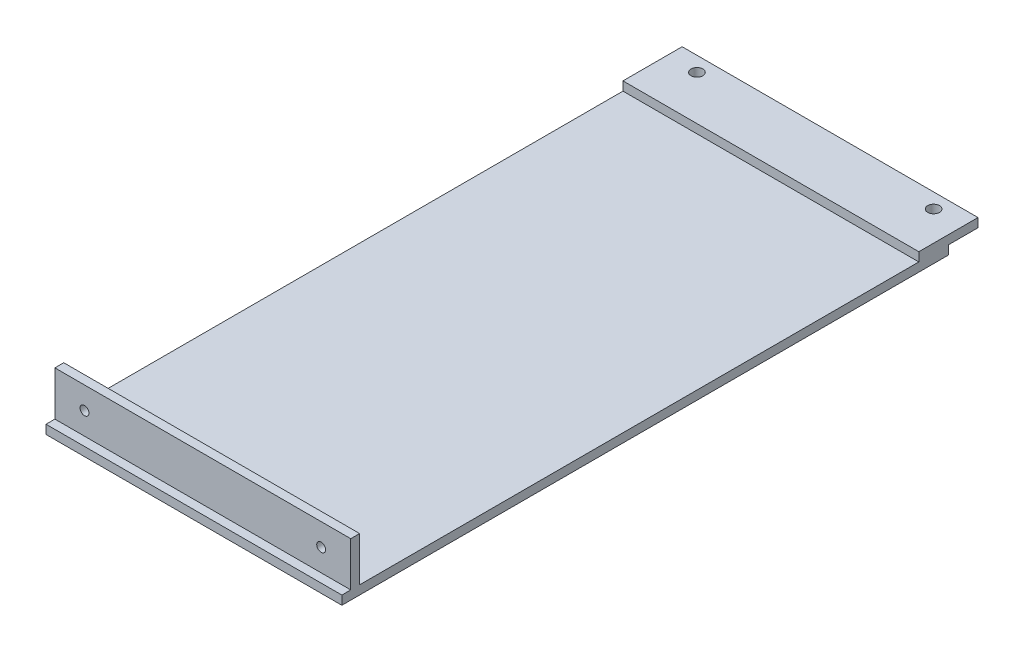
SolidWorks part; units mm, degrees
ref_plane "Front Plane" through (0, 0, 0) normal (0, 0, 1) x (1, 0, 0)
ref_plane "Top Plane" through (0, 0, 0) normal (0, 1, 0) x (1, 0, 0)
ref_plane "Right Plane" through (0, 0, 0) normal (1, 0, 0) x (0, 0, -1)
sketch "Sketch1" plane through (0, 0, 0) normal (0, 1, 0) x (1, 0, 0)
  line L1 (-50, -102.5) -> (50, -102.5)
  line L2 (-50, -102.5) -> (-50, 102.5)
  line L3 (-50, 102.5) -> (50, 102.5)
  line L4 (50, -102.5) -> (50, 102.5)
  line L5 (-50, -102.5) -> (50, 102.5) construction
  line L6 (-50, 102.5) -> (50, -102.5) construction
  point P0 (0, 0)
  dimension "D1" = 205
  dimension "D2" = 100
extrude "Boss-Extrude1" add sketch "Sketch1" along normal blind 3 contours L2 L3 L4 L1
sketch "Sketch2" plane through (0, 3, 0) normal (0, 1, 0) x (1, 0, 0)
  line L0 (-50, -102.5) -> (-50, 102.5) construction
  line L1 (-50, 92.5) -> (50, 92.5)
  line L2 (-50, 92.5) -> (-50, 112.5)
  line L3 (-50, 112.5) -> (50, 112.5)
  line L4 (50, 92.5) -> (50, 112.5)
  line L5 (50, -102.5) -> (50, 102.5) construction
  line L6 (-50, 102.5) -> (50, 102.5) construction
  dimension "D1" = 10
  dimension "D2" = 10
extrude "Boss-Extrude2" add sketch "Sketch2" along normal blind 3
sketch "Sketch3" plane through (0, 6, 0) normal (0, 1, 0) x (1, 0, 0)
  line L0 (50, 112.5) -> (-50, 112.5) construction
  line L1 (-50, 112.5) -> (-50, 92.5) construction
  circle A0 centre (-40, 107.5) radius 2
  dimension "D1" = 4
  dimension "D2" = 5
  dimension "D3" = 10
extrude "Cut-Extrude1" cut sketch "Sketch3" against normal up to next
pattern_linear "LPattern1" count 2 spacing 80 along (1, 0, 0) of "Cut-Extrude1"
sketch "Sketch4" plane through (0, 3, 0) normal (0, 1, 0) x (1, 0, 0)
  line L0 (-50, -102.5) -> (-50, 92.5) construction
  line L1 (-50, -99.5) -> (50, -99.5)
  line L2 (-50, -99.5) -> (-50, -96.5)
  line L3 (-50, -96.5) -> (50, -96.5)
  line L4 (50, -99.5) -> (50, -96.5)
  line L5 (50, -102.5) -> (50, 92.5) construction
  line L6 (-50, -102.5) -> (50, -102.5) construction
  dimension "D1" = 3
  dimension "D2" = 3
extrude "Boss-Extrude3" add sketch "Sketch4" along normal blind 15
sketch "Sketch5" plane through (0, 0, 99.5) normal (0, 0, 1) x (1, 0, 0)
  line L0 (-50, 18) -> (-50, 3) construction
  line L1 (-50, 18) -> (50, 18) construction
  circle A0 centre (-40, 10.5) radius 1.5
  point P6 (0, 0)
  dimension "D1" = 3
  dimension "D2" = 10
  dimension "D3" = 7.5
extrude "Cut-Extrude2" cut sketch "Sketch5" against normal up to next
pattern_linear "LPattern2" count 2 spacing 80 along (1, 0, 0) of "Cut-Extrude2"
